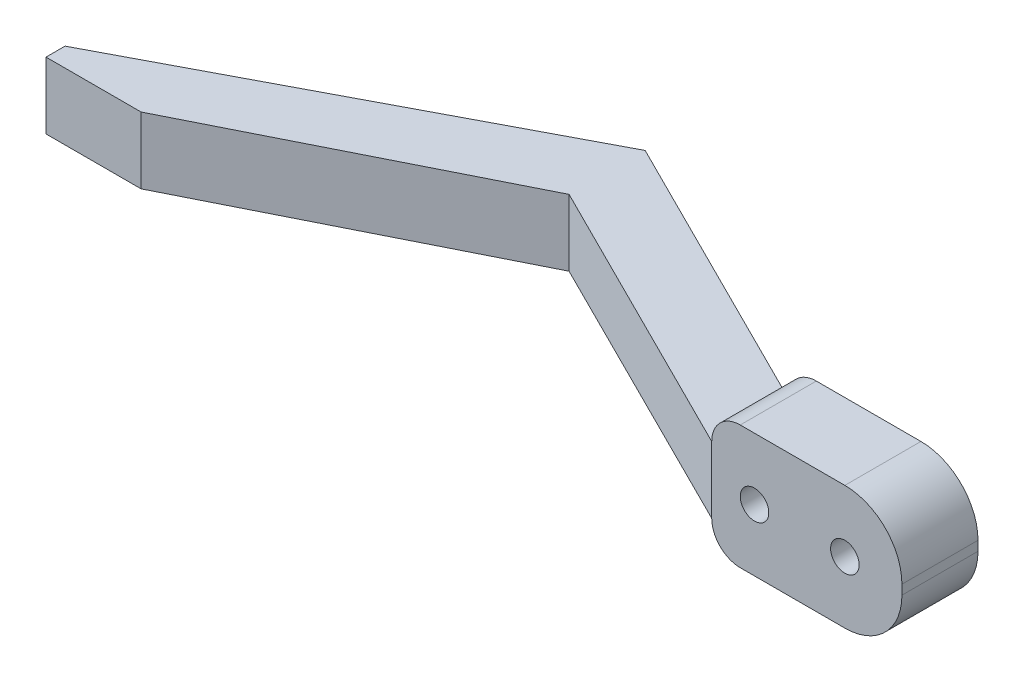
SolidWorks part; units mm, degrees
ref_plane "Front Plane" through (0, 0, 0) normal (0, 0, 1) x (1, 0, 0)
ref_plane "Top Plane" through (0, 0, 0) normal (0, 1, 0) x (1, 0, 0)
ref_plane "Right Plane" through (0, 0, 0) normal (1, 0, 0) x (0, 0, -1)
sketch "Sketch1" plane through (0, 0, 0) normal (0, 1, 0) x (1, 0, 0)
  line L0 (0, 0) -> (-30, 0)
  line L1 (0, 0) -> (0, 15)
  line L2 (0, 0) -> (30, 0)
  line L3 (-30, 0) -> (0, 15)
  line L4 (0, 15) -> (30, 0)
  line L5 (-30, 0) -> (-40, 0)
  line L6 (-40, 0) -> (-40, 2)
  line L7 (-40, 2) -> (0, 23)
  line L8 (0, 23) -> (30, 8)
  line L9 (30, 0) -> (50, 0)
  line L10 (50, 0) -> (50, 8)
  line L11 (50, 8) -> (30, 8)
  dimension "D1" = 30
  dimension "D2" = 15
  dimension "D3" = 30
  dimension "D4" = 10
  dimension "D5" = 2
  dimension "D6" = 8
  dimension "D7" = 0
  dimension "D8" = 8
  dimension "D9" = 20
extrude "Boss-Extrude1" add sketch "Sketch1" along normal blind 7 contours L10 L11 L8 L7 L6 L5 L3 L4 L9 region at (-35, 0, -0.9289)
sketch "Sketch2" plane through (0, 7, 0) normal (0, 1, 0) x (1, 0, 0)
  line L0 (30, 8) -> (30, 0)
  line L1 (30, 0) -> (50, 0)
  line L2 (50, 0) -> (50, 8)
  line L3 (50, 8) -> (30, 8)
extrude "Boss-Extrude2" add sketch "Sketch2" along normal blind 3 and the other way blind 10
fillet "Fillet1" radius 6 2 edges at (50, 10, -4) (50, -3, -4)
fillet "Fillet2" radius 3 2 edges at (30, -3, -4) (30, 10, -4)
hole_wizard "Ø3.0 (3) Diameter Hole1" positions "Sketch3" profile "Sketch4" hole size "Ø3.0" standard "ISO" end condition through all
sketch "Sketch3" plane through (0, 0, -8) normal (0, 0, -1) x (-1, 0, 0)
  line L0 (-50, 4) -> (-50, 3) construction
  point P0 (-44, 3.5)
  point P2 (-34.5, 3.5)
  point P7 (-50, 3.5)
  point P12 (-41.1099, -8.0998)
  dimension "D1" = 6
  dimension "D2" = 9.5
sketch "Sketch4" plane through (44, 3.5, -8) normal (1, 0, 0) x (0, 1, 0)
  line L0 (0, 0) -> (0, 8)
  line L1 (0, 8) -> (1.5, 8)
  line L2 (1.5, 8) -> (1.5, 0)
  line L5 (1.5, 0) -> (0, 0)
  line L11 (0, -6.35) -> (0, 107.95) construction
  dimension "Thru Hole Dia." = 3
  dimension "Thru Hole Depth" = 8
